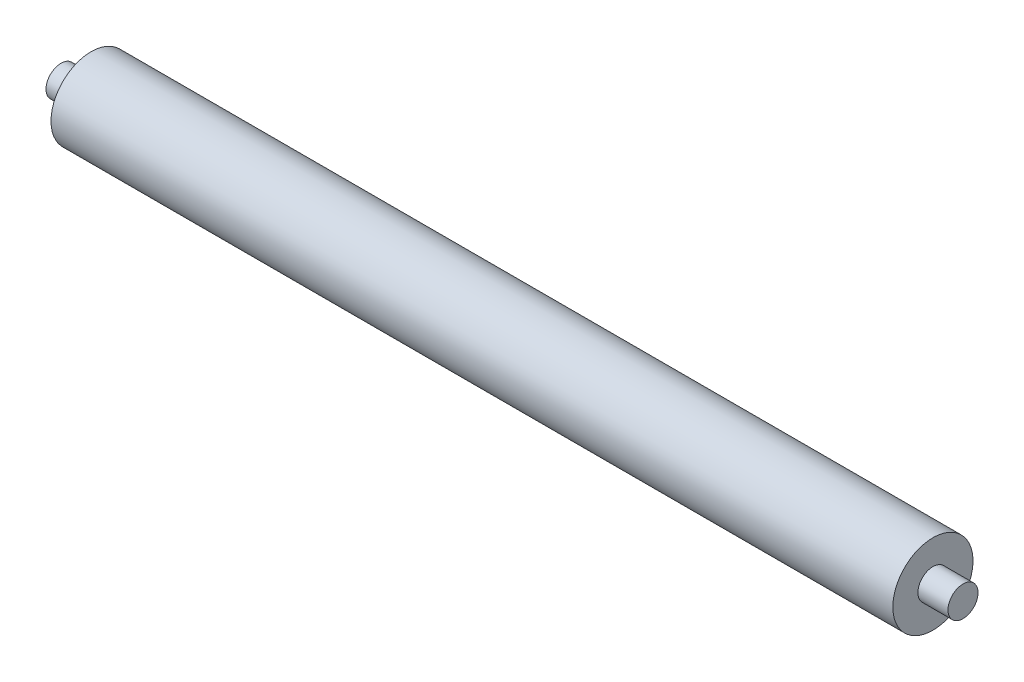
SolidWorks part; units mm, degrees
ref_plane "Plan de face" through (0, 0, 0) normal (0, 0, 1) x (1, 0, 0)
ref_plane "Plan de dessus" through (0, 0, 0) normal (0, 1, 0) x (1, 0, 0)
ref_plane "Plan de droite" through (0, 0, 0) normal (1, 0, 0) x (0, 0, -1)
sketch "Esquisse1" plane through (0, 0, 0) normal (0, 0, 1) x (1, 0, 0)
  line L0 (0, 0) -> (90, 0)
  line L1 (90, 0) -> (90, 1.5)
  line L2 (90, 1.5) -> (87, 1.5)
  line L3 (87, 1.5) -> (87, 4)
  line L4 (87, 4) -> (3, 4)
  line L5 (3, 4) -> (3, 1.5)
  line L6 (3, 1.5) -> (0, 1.5)
  line L7 (0, 1.5) -> (0, 0)
  dimension "D1" = 1.5
  dimension "D2" = 4
  dimension "D3" = 3
  dimension "D4" = 90
revolve "Révolution1" add sketch "Esquisse1" angle 360 about L0
